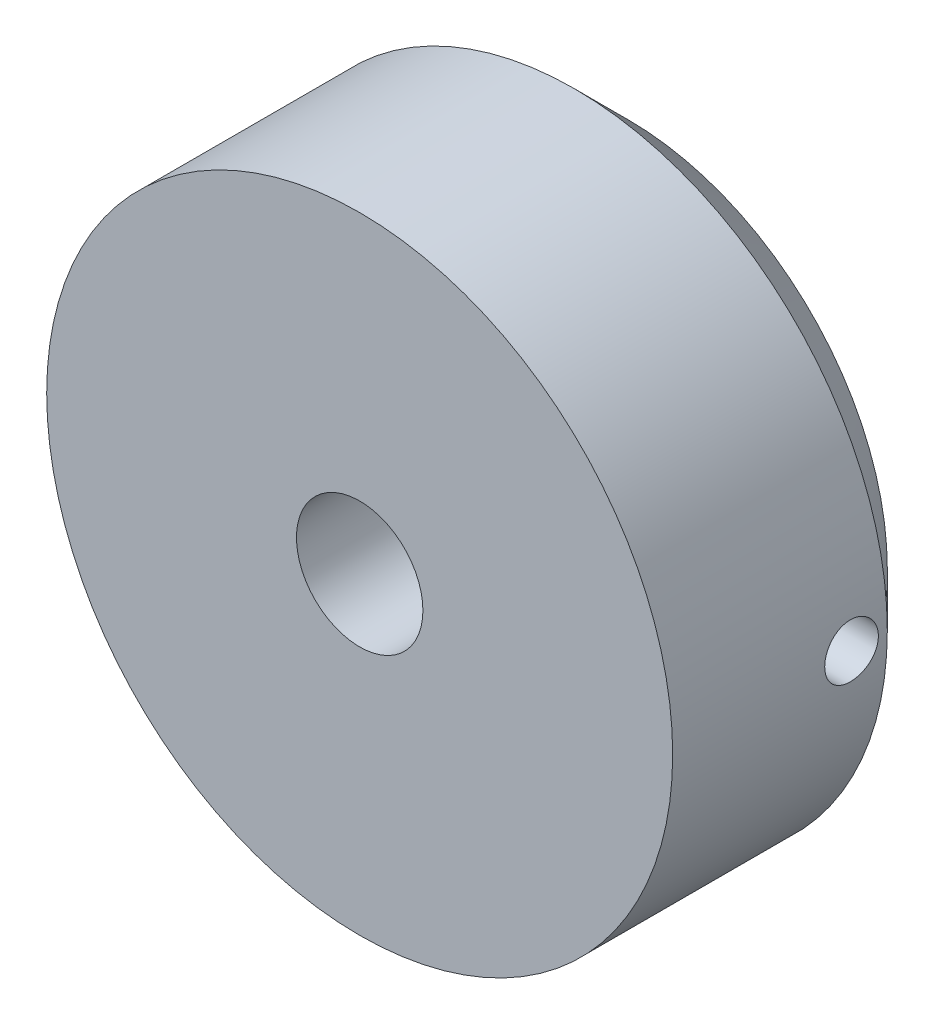
SolidWorks part; units mm, degrees
ref_plane "Front Plane" through (0, 0, 0) normal (0, 0, 1) x (1, 0, 0)
ref_plane "Top Plane" through (0, 0, 0) normal (0, 1, 0) x (1, 0, 0)
ref_plane "Right Plane" through (0, 0, 0) normal (1, 0, 0) x (0, 0, -1)
ref_axis "Z" through (0, 0, 543.0939) along (0, 0, -1)
ref_axis "X" through (17.0818, 0, 0) along (-1, 0, 0)
ref_axis "Y" through (0, 33, 0) along (0, -1, 0)
sketch "Sketch1" plane through (0, 0, 0) normal (0, 0, 1) x (1, 0, 0)
  circle A0 centre (0, 0) radius 17.5
  circle A1 centre (0, 0) radius 3.535
  dimension "D1" = 35
  dimension "D2" = 7.07
extrude "Boss-Extrude1" add sketch "Sketch1" against normal blind 5 and the other way blind 10
sketch "Sketch2" plane through (0, 0, 0) normal (0, 1, 0) x (1, 0, 0)
  line L0 (-33, 0) -> (33, 0) construction
  line L1 (0, -8.25) -> (0, 8.25) construction
  circle A0 centre (0, 0) radius 1.5
  dimension "D1" = 3
extrude "Cut-Extrude1" cut sketch "Sketch2" against normal through all
sketch "Sketch3" plane through (0, 0, 0) normal (1, 0, 0) x (0, 0, -1)
  circle A0 centre (0, 0) radius 1.5
  dimension "D1" = 3
extrude "Cut-Extrude2" cut sketch "Sketch3" along normal through all
chamfer "Chamfer1" distance 3 angle 45 1 edges at (17.5, 0, -5)
sketch "Sketch4" plane through (0, 0, 0) normal (0, 0, 1) x (1, 0, 0)
  circle A0 centre (0, 0) radius 3.535
  circle A2 centre (0, 0) radius 3.535 construction
  circle A3 centre (0, 0) radius 11.5
  dimension "D1" = 23
extrude "Boss-Extrude2" add sketch "Sketch4" along normal up to surface and the other way up to surface up to face at (17.5, 0, 10) other way up to face at (14.5, 0, -5)
sketch "Sketch5" plane through (0, 0, 0) normal (0, 0, 1) x (1, 0, 0)
  line L0 (0, 0) -> (0, -37.34) construction
  point P2 (0, 0)
  point P3 (8.8296, -36.281)
  dimension "D1" = 37.34
equation "\"EyeDiameter\" = 35"
equation "\"BasePlaneDistance\" = \"EyeDiameter\"/2+19.84"
equation "\"EyeClearance\" = 2"
equation "\"EyeOD\"= \"EyeDiameter\""
equation "\"D1@Sketch1\"=\"EyeOD\""
equation "\"D2@Sketch1\"= 7.07"
equation "\"pinHoleDiameter\"= 3"
equation "\"D1@Sketch2\"=\"pinHoleDiameter\""
equation "\"D1@Sketch3\"=\"pinHoleDiameter\""
equation "\"D1@Sketch4\"=\"EyeDiameter\"-12"
equation "\"D1@Sketch5\"=\"BasePlaneDistance\""
